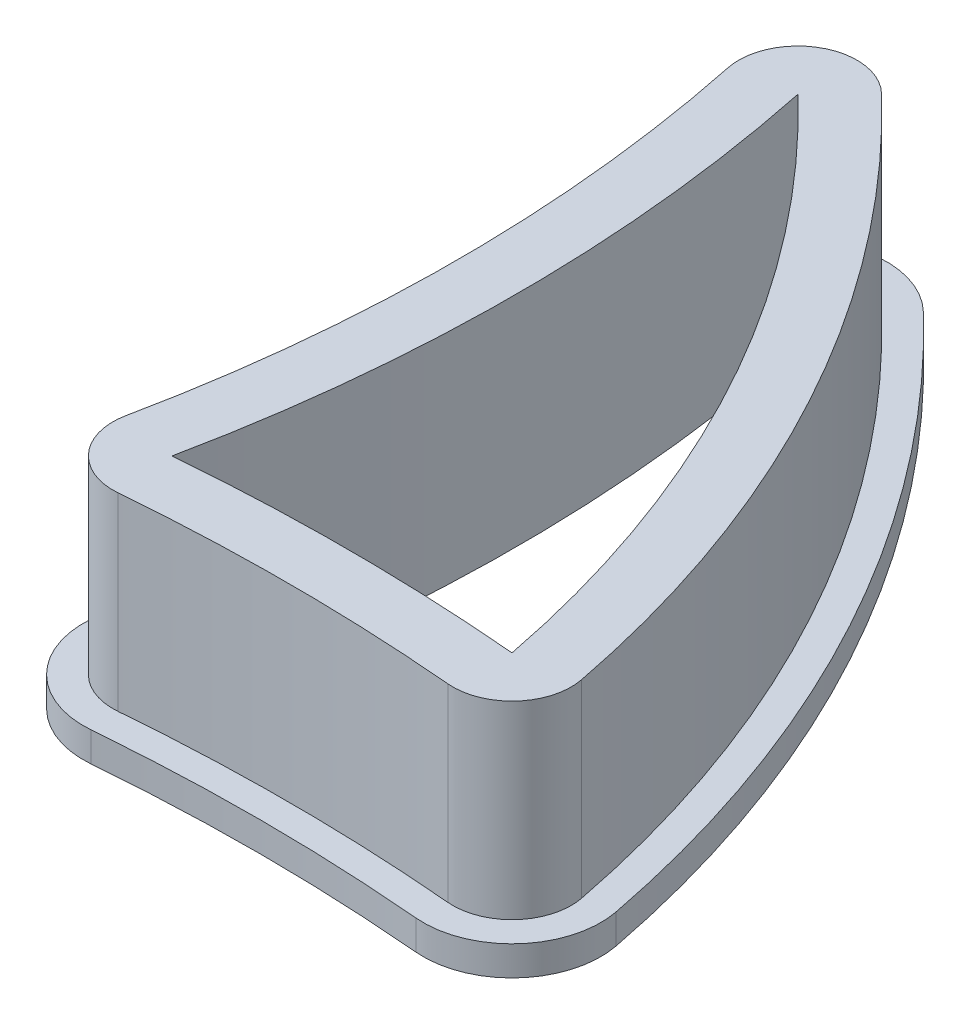
SolidWorks part; units mm, degrees
ref_plane "前视基准面" through (0, 0, 0) normal (0, 0, 1) x (1, 0, 0)
ref_plane "上视基准面" through (0, 0, 0) normal (0, 1, 0) x (1, 0, 0)
ref_plane "右视基准面" through (0, 0, 0) normal (1, 0, 0) x (0, 0, -1)
other "Configuration Table"
sketch "草图1" plane through (0, 0, 0) normal (0, 1, 0) x (1, 0, 0)
  line L0 (0, 6.7412) -> (0, -5.5856) construction
  line L1 (-1.0272, 6.9158) -> (15.4407, 6.9158) construction
  arc A0 (-8.25, 6.9158) -> (8.25, 6.9158) centre (0, -57.5585) cw
  arc A1 (8.25, 6.9158) -> (-9.25, 35.9158) centre (-33.4069, 1.5582) ccw
  arc A2 (-9.25, 35.9158) -> (-8.25, 6.9158) centre (-56.5703, 19.7669) cw
  arc A3 (-11.2574, 38.4147) -> (-9.629, 5.713) centre (-56.5703, 19.7669) cw
  arc A4 (-9.629, 5.713) -> (9.3884, 5.7492) centre (0, -57.5585) cw
  arc A5 (9.3884, 5.7492) -> (-11.2574, 38.4147) centre (-33.4069, 1.5582) ccw
  arc A6 (-5.6635, 30.3732) -> (-5.6547, 9.2025) centre (-56.5703, 19.7669) cw
  arc A7 (-5.6547, 9.2025) -> (5.8593, 9.1848) centre (0, -57.5585) cw
  arc A8 (5.8593, 9.1848) -> (-5.6635, 30.3732) centre (-33.4069, 1.5582) ccw
  dimension "D2" = 65
  dimension "D3" = 50
  dimension "D4" = 42
  dimension "D1" = 16.5
  dimension "D5" = 29
  dimension "D6" = 17.5
  dimension "D7" = 1
  dimension "D8" = 2
extrude "凸台-拉伸7" add sketch "草图1" along normal blind 6.4 contours A1 A2 A0 | A8 A6 A7
extrude "凸台-拉伸8" add sketch "草图1<9>" against normal blind 1 contours A5 A3 A4
sketch "草图1<9>" plane through (0, 0, 0) normal (0, 1, 0) x (1, 0, 0) same geometry as "草图1"
fillet "圆角1" radius 2 3 edges at (-8.25, 3.2, -6.9158) (8.25, 3.2, -6.9158) (-9.25, 3.2, -35.9158)
fillet "圆角4" radius 3 3 edges at (-9.629, -0.5, -5.713) (9.3884, -0.5, -5.7492) (-11.2574, -0.5, -38.4147)
extrude "切除-拉伸1" cut sketch "草图1<10>" against normal through all contours A7 A8 A6 region at (-0.883, 0, -16.8145)
sketch "草图1<10>" plane through (0, 0, 0) normal (0, 1, 0) x (1, 0, 0) same geometry as "草图1"
